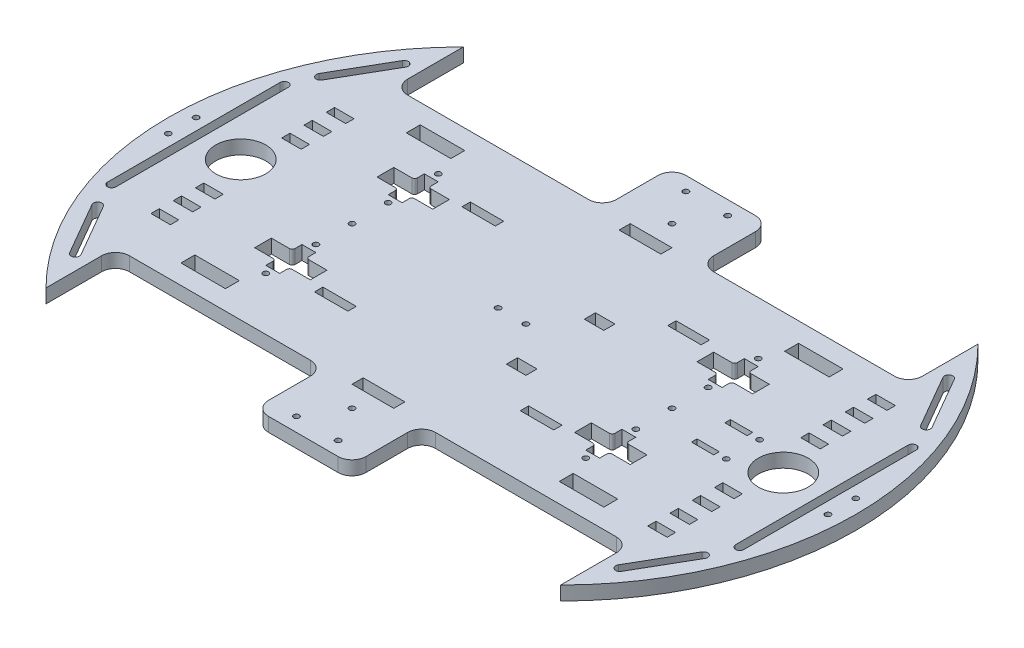
SolidWorks part; units mm, degrees
ref_plane "Front Plane" through (0, 0, 0) normal (0, 0, 1) x (1, 0, 0)
ref_plane "Top Plane" through (0, 0, 0) normal (0, 1, 0) x (1, 0, 0)
ref_plane "Right Plane" through (0, 0, 0) normal (1, 0, 0) x (0, 0, -1)
sketch "Sketch1" plane through (0, 0, 0) normal (0, 1, 0) x (1, 0, 0)
  line L2 (-12.5, 75) -> (12.5, 75)
  line L4 (-17.5, 70) -> (-17.5, 55)
  line L6 (-87.5, 50) -> (-22.5, 50)
  line L7 (87.5, 50) -> (22.5, 50)
  line L8 (17.5, 70) -> (17.5, 55)
  line L9 (-92.5, 55) -> (-92.5, 75)
  line L10 (92.5, 75) -> (92.5, 55)
  line L11 (92.5, -75) -> (92.5, -55)
  line L12 (-92.5, -55) -> (-92.5, -75)
  line L13 (17.5, -70) -> (17.5, -55)
  line L14 (87.5, -50) -> (22.5, -50)
  line L15 (-87.5, -50) -> (-22.5, -50)
  line L16 (-17.5, -70) -> (-17.5, -55)
  line L17 (-12.5, -75) -> (12.5, -75)
  arc A0 (-17.5, 55) -> (-22.5, 50) centre (-22.5, 55) cw
  arc A1 (17.5, 55) -> (22.5, 50) centre (22.5, 55) ccw
  arc A2 (-92.5, 55) -> (-87.5, 50) centre (-87.5, 55) ccw
  arc A3 (92.5, 55) -> (87.5, 50) centre (87.5, 55) cw
  arc A4 (92.5, -55) -> (87.5, -50) centre (87.5, -55) ccw
  arc A5 (-92.5, -55) -> (-87.5, -50) centre (-87.5, -55) cw
  arc A6 (17.5, -55) -> (22.5, -50) centre (22.5, -55) cw
  arc A7 (-17.5, -55) -> (-22.5, -50) centre (-22.5, -55) ccw
  arc A8 (92.5, -75) -> (92.5, 75) centre (17.5, 0) ccw
  arc A9 (-92.5, -75) -> (-92.5, 75) centre (-17.5, 0) cw
  arc A10 (12.5, -75) -> (17.5, -70) centre (12.5, -70) ccw
  arc A11 (-12.5, -75) -> (-17.5, -70) centre (-12.5, -70) cw
  arc A12 (12.5, 75) -> (17.5, 70) centre (12.5, 70) cw
  arc A13 (-12.5, 75) -> (-17.5, 70) centre (-12.5, 70) ccw
  point P20 (-92.5, 50)
  point P24 (92.5, 50)
  point P41 (92.5, -50)
  point P42 (-92.5, -50)
  point P47 (17.5, -75)
  point P50 (-17.5, -75)
  point P53 (17.5, 75)
  point P56 (-17.5, 75)
  dimension "D5" = 5
  dimension "D6" = 5
  dimension "D7" = 5
  dimension "D8" = 5
  dimension "D2" = 75
  dimension "D4" = 25
extrude "Boss-Extrude1" add sketch "Sketch1" along normal blind 5 contours L6 A0 L4 A13 L2 A12 L8 A1 L7 A3 L10 A8 L11 A4 L14 A6 L13 A10 L17 A11 L16 A7 L15 A5 L12 A9 L9 A2
sketch "Sketch2" plane through (0, 5, 0) normal (0, 1, 0) x (1, 0, 0)
  line L0 (-12.5, 75) -> (12.5, 75) construction
  line L1 (0, 31) -> (0, -27.6021)
  line L2 (-7.5, 50) -> (7.5, 50)
  line L3 (-7.5, 50) -> (-7.5, 46)
  line L4 (-7.5, 46) -> (7.5, 46)
  line L5 (7.5, 50) -> (7.5, 46)
  line L6 (-145.8755, 0) -> (156.3391, 0)
  line L7 (7.5, -50) -> (7.5, -46)
  line L8 (-7.5, -46) -> (7.5, -46)
  line L9 (-7.5, -50) -> (-7.5, -46)
  line L10 (-7.5, -50) -> (7.5, -50)
  line L11 (-92.5, 55) -> (-92.5, 75) construction
  line L12 (111.3751, -31) -> (111.3751, 31)
  line L14 (-111.3751, -31) -> (-111.3751, 31)
  line L16 (-114.3751, -31) -> (-114.3751, 31)
  line L17 (-111.3751, -32.5) -> (-114.3751, 32.5) construction
  line L18 (-111.3751, 32.5) -> (-114.3751, -32.5) construction
  line L19 (114.3751, -31) -> (114.3751, 31)
  line L20 (-87.5, 50) -> (-22.5, 50) construction
  line L21 (-96.7856, 25) -> (-89.7856, 25)
  line L22 (-96.7856, 25) -> (-96.7856, 22)
  line L23 (-96.7856, 22) -> (-89.7856, 22)
  line L24 (-89.7856, 25) -> (-89.7856, 22)
  line L25 (-96.7856, 25) -> (-89.7856, 22) construction
  line L26 (-96.7856, 22) -> (-89.7856, 25) construction
  line L27 (-89.7856, 30) -> (-96.7856, 30)
  line L28 (-89.7856, 30) -> (-89.7856, 33)
  line L29 (-89.7856, 33) -> (-96.7856, 33)
  line L30 (-96.7856, 30) -> (-96.7856, 33)
  line L31 (-89.7856, 30) -> (-96.7856, 33) construction
  line L32 (-89.7856, 33) -> (-96.7856, 30) construction
  line L33 (-89.7856, 14) -> (-96.7856, 14)
  line L34 (-89.7856, 14) -> (-89.7856, 17)
  line L35 (-89.7856, 17) -> (-96.7856, 17)
  line L36 (-96.7856, 14) -> (-96.7856, 17)
  line L37 (-89.7856, 14) -> (-96.7856, 17) construction
  line L38 (-89.7856, 17) -> (-96.7856, 14) construction
  line L39 (-89.7856, -17) -> (-96.7856, -14) construction
  line L40 (-89.7856, -14) -> (-96.7856, -17) construction
  line L41 (-89.7856, -33) -> (-96.7856, -30) construction
  line L42 (-89.7856, -30) -> (-96.7856, -33) construction
  line L43 (-96.7856, -22) -> (-89.7856, -25) construction
  line L44 (-96.7856, -25) -> (-89.7856, -22) construction
  line L45 (-96.7856, -14) -> (-96.7856, -17)
  line L46 (-89.7856, -17) -> (-96.7856, -17)
  line L47 (-89.7856, -14) -> (-89.7856, -17)
  line L48 (-89.7856, -14) -> (-96.7856, -14)
  line L49 (-96.7856, -30) -> (-96.7856, -33)
  line L50 (-89.7856, -33) -> (-96.7856, -33)
  line L51 (-89.7856, -30) -> (-89.7856, -33)
  line L52 (-89.7856, -30) -> (-96.7856, -30)
  line L53 (-89.7856, -25) -> (-89.7856, -22)
  line L54 (-96.7856, -22) -> (-89.7856, -22)
  line L55 (-96.7856, -25) -> (-96.7856, -22)
  line L56 (-96.7856, -25) -> (-89.7856, -25)
  line L57 (89.7856, 17) -> (96.7856, 14) construction
  line L58 (89.7856, 14) -> (96.7856, 17) construction
  line L59 (89.7856, 33) -> (96.7856, 30) construction
  line L60 (89.7856, 30) -> (96.7856, 33) construction
  line L61 (96.7856, 22) -> (89.7856, 25) construction
  line L62 (96.7856, 25) -> (89.7856, 22) construction
  line L63 (96.7856, 14) -> (96.7856, 17)
  line L64 (89.7856, 17) -> (96.7856, 17)
  line L65 (89.7856, 14) -> (89.7856, 17)
  line L66 (89.7856, 14) -> (96.7856, 14)
  line L67 (96.7856, 30) -> (96.7856, 33)
  line L68 (89.7856, 33) -> (96.7856, 33)
  line L69 (89.7856, 30) -> (89.7856, 33)
  line L70 (89.7856, 30) -> (96.7856, 30)
  line L71 (89.7856, 25) -> (89.7856, 22)
  line L72 (96.7856, 22) -> (89.7856, 22)
  line L73 (96.7856, 25) -> (96.7856, 22)
  line L74 (96.7856, 25) -> (89.7856, 25)
  line L75 (96.7856, -25) -> (89.7856, -22) construction
  line L76 (96.7856, -22) -> (89.7856, -25) construction
  line L77 (89.7856, -30) -> (96.7856, -33) construction
  line L78 (89.7856, -33) -> (96.7856, -30) construction
  line L79 (89.7856, -14) -> (96.7856, -17) construction
  line L80 (89.7856, -17) -> (96.7856, -14) construction
  line L81 (96.7856, -25) -> (89.7856, -25)
  line L82 (96.7856, -25) -> (96.7856, -22)
  line L83 (96.7856, -22) -> (89.7856, -22)
  line L84 (89.7856, -25) -> (89.7856, -22)
  line L85 (89.7856, -30) -> (96.7856, -30)
  line L86 (89.7856, -30) -> (89.7856, -33)
  line L87 (89.7856, -33) -> (96.7856, -33)
  line L88 (96.7856, -30) -> (96.7856, -33)
  line L89 (89.7856, -14) -> (96.7856, -14)
  line L90 (89.7856, -14) -> (89.7856, -17)
  line L91 (89.7856, -17) -> (96.7856, -17)
  line L92 (96.7856, -14) -> (96.7856, -17)
  line L93 (96.7856, -38) -> (89.7856, -41) construction
  line L94 (96.7856, 41) -> (89.7856, 41)
  line L95 (96.7856, 41) -> (96.7856, 38)
  line L96 (96.7856, 38) -> (89.7856, 38)
  line L97 (89.7856, 41) -> (89.7856, 38)
  line L98 (96.7856, 41) -> (89.7856, 38) construction
  line L99 (96.7856, 38) -> (89.7856, 41) construction
  line L100 (96.7856, -41) -> (89.7856, -38) construction
  line L101 (89.7856, -41) -> (89.7856, -38)
  line L102 (96.7856, -38) -> (89.7856, -38)
  line L103 (96.7856, -41) -> (96.7856, -38)
  line L104 (96.7856, -41) -> (89.7856, -41)
  line L105 (-54, 25) -> (-47.5, 25)
  line L106 (-60, 28.5) -> (-55, 28.5)
  line L107 (-60, 28.5) -> (-60, 26)
  line L108 (-60, 15.5) -> (-55, 15.5)
  line L109 (-55, 28.5) -> (-55, 26)
  line L110 (-67.5, 25) -> (-61, 25)
  line L111 (-67.5, 25) -> (-67.5, 19)
  line L112 (-67.5, 19) -> (-61, 19)
  line L113 (-47.5, 25) -> (-47.5, 19)
  line L114 (-60, 18) -> (-60, 15.5)
  line L115 (-54, 19) -> (-47.5, 19)
  line L116 (-55, 18) -> (-55, 15.5)
  line L117 (-17.5, 70) -> (-17.5, 55) construction
  line L118 (-55, -18) -> (-55, -15.5)
  line L119 (-54, -19) -> (-47.5, -19)
  line L120 (-60, -18) -> (-60, -15.5)
  line L121 (-47.5, -25) -> (-47.5, -19)
  line L122 (-67.5, -19) -> (-61, -19)
  line L123 (-67.5, -25) -> (-67.5, -19)
  line L124 (-67.5, -25) -> (-61, -25)
  line L125 (-55, -28.5) -> (-55, -26)
  line L126 (-60, -15.5) -> (-55, -15.5)
  line L127 (-60, -28.5) -> (-60, -26)
  line L128 (-60, -28.5) -> (-55, -28.5)
  line L129 (-54, -25) -> (-47.5, -25)
  line L130 (54, -25) -> (47.5, -25)
  line L131 (60, -28.5) -> (55, -28.5)
  line L132 (60, -28.5) -> (60, -26)
  line L133 (60, -15.5) -> (55, -15.5)
  line L134 (55, -28.5) -> (55, -26)
  line L135 (67.5, -25) -> (61, -25)
  line L136 (67.5, -25) -> (67.5, -19)
  line L137 (67.5, -19) -> (61, -19)
  line L138 (47.5, -25) -> (47.5, -19)
  line L139 (60, -18) -> (60, -15.5)
  line L140 (54, -19) -> (47.5, -19)
  line L141 (55, -18) -> (55, -15.5)
  line L142 (55, 18) -> (55, 15.5)
  line L143 (54, 19) -> (47.5, 19)
  line L144 (60, 18) -> (60, 15.5)
  line L145 (47.5, 25) -> (47.5, 19)
  line L146 (67.5, 19) -> (61, 19)
  line L147 (67.5, 25) -> (67.5, 19)
  line L148 (67.5, 25) -> (61, 25)
  line L149 (55, 28.5) -> (55, 26)
  line L150 (60, 15.5) -> (55, 15.5)
  line L151 (60, 28.5) -> (60, 26)
  line L152 (60, 28.5) -> (55, 28.5)
  line L153 (54, 25) -> (47.5, 25)
  line L154 (-42.9867, -28) -> (-42.9867, -25)
  line L155 (-42.9867, 28) -> (-30.9867, 28)
  line L156 (-42.9867, 28) -> (-42.9867, 25)
  line L157 (-42.9867, 25) -> (-30.9867, 25)
  line L158 (-30.9867, 28) -> (-30.9867, 25)
  line L159 (-42.9867, -25) -> (-30.9867, -25)
  line L160 (-30.9867, -28) -> (-30.9867, -25)
  line L161 (-42.9867, -28) -> (-30.9867, -28)
  line L162 (42.9867, 28) -> (42.9867, 25)
  line L163 (30.9867, 28) -> (30.9867, 25)
  line L164 (42.9867, 28) -> (30.9867, 28)
  line L165 (42.9867, 25) -> (30.9867, 25)
  line L166 (42.9867, -28) -> (30.9867, -28)
  line L167 (30.9867, -28) -> (30.9867, -25)
  line L168 (42.9867, -25) -> (30.9867, -25)
  line L169 (42.9867, -28) -> (42.9867, -25)
  line L170 (87.5, 50) -> (22.5, 50) construction
  line L171 (14, 16) -> (21, 16)
  line L172 (14, 16) -> (14, 12)
  line L173 (14, 12) -> (21, 12)
  line L174 (21, 16) -> (21, 12)
  line L175 (17.5, 70) -> (17.5, 55) construction
  line L176 (21, -16) -> (21, -12)
  line L177 (14, -12) -> (21, -12)
  line L178 (14, -16) -> (14, -12)
  line L179 (14, -16) -> (21, -16)
  line L180 (-110.1643, 40.799) -> (-99.1643, 59.8516)
  line L182 (-110.1643, -40.799) -> (-99.1643, -59.8516)
  line L184 (-107.5662, -39.299) -> (-96.5662, -58.3516)
  line L185 (-107.5662, 39.299) -> (-96.5662, 58.3516)
  line L186 (110.1643, 40.799) -> (99.1643, 59.8516)
  line L187 (107.5662, 39.299) -> (96.5662, 58.3516)
  line L188 (110.1643, -40.799) -> (99.1643, -59.8516)
  line L189 (107.5662, -39.299) -> (96.5662, -58.3516)
  circle A0 centre (0, 57.5) radius 1
  circle A1 centre (-7.5, 70) radius 1
  circle A2 centre (7.5, 70) radius 1
  circle A3 centre (7.5, -70) radius 1
  circle A4 centre (-7.5, -70) radius 1
  circle A5 centre (0, -57.5) radius 1
  circle A6 centre (-97.5, 0) radius 9
  arc A7 (-114.3751, 31) -> (-111.3751, 31) centre (-112.8751, 31) cw
  arc A8 (-114.3751, -31) -> (-111.3751, -31) centre (-112.8751, -31) ccw
  circle A9 centre (-118.566, 5) radius 1
  arc A10 (-92.5, 75) -> (-92.5, -75) centre (-17.5, 0) ccw construction
  circle A11 centre (-118.566, -5) radius 1
  circle A12 centre (118.566, -5) radius 1
  circle A13 centre (118.566, 5) radius 1
  arc A14 (114.3751, 31) -> (111.3751, 31) centre (112.8751, 31) ccw
  arc A15 (114.3751, -31) -> (111.3751, -31) centre (112.8751, -31) cw
  circle A16 centre (97.5, 0) radius 9
  arc A17 (-55, 26) -> (-54, 25) centre (-54, 26) ccw
  arc A18 (-54, 19) -> (-55, 18) centre (-54, 18) ccw
  arc A19 (-60, 18) -> (-61, 19) centre (-61, 18) ccw
  arc A20 (-61, 25) -> (-60, 26) centre (-61, 26) ccw
  arc A21 (-61, -25) -> (-60, -26) centre (-61, -26) cw
  arc A22 (-60, -18) -> (-61, -19) centre (-61, -18) cw
  arc A23 (-54, -19) -> (-55, -18) centre (-54, -18) cw
  arc A24 (-55, -26) -> (-54, -25) centre (-54, -26) cw
  arc A25 (55, -26) -> (54, -25) centre (54, -26) ccw
  arc A26 (54, -19) -> (55, -18) centre (54, -18) ccw
  arc A27 (60, -18) -> (61, -19) centre (61, -18) ccw
  arc A28 (61, -25) -> (60, -26) centre (61, -26) ccw
  arc A29 (61, 25) -> (60, 26) centre (61, 26) cw
  arc A30 (60, 18) -> (61, 19) centre (61, 18) cw
  arc A31 (54, 19) -> (55, 18) centre (54, 18) cw
  arc A32 (55, 26) -> (54, 25) centre (54, 26) cw
  circle A34 centre (5, 0) radius 1
  circle A35 centre (-5, 0) radius 1
  arc A36 (-110.1643, -40.799) -> (-107.5662, -39.299) centre (-108.8653, -40.049) cw
  arc A37 (-99.1643, -59.8516) -> (-96.5662, -58.3516) centre (-97.8653, -59.1016) ccw
  arc A38 (-99.1643, 59.8516) -> (-96.5662, 58.3516) centre (-97.8653, 59.1016) cw
  arc A39 (-110.1643, 40.799) -> (-107.5662, 39.299) centre (-108.8653, 40.049) ccw
  arc A40 (110.1643, 40.799) -> (107.5662, 39.299) centre (108.8653, 40.049) cw
  arc A41 (99.1643, 59.8516) -> (96.5662, 58.3516) centre (97.8653, 59.1016) ccw
  arc A42 (110.1643, -40.799) -> (107.5662, -39.299) centre (108.8653, -40.049) ccw
  arc A43 (99.1643, -59.8516) -> (96.5662, -58.3516) centre (97.8653, -59.1016) cw
  circle A44 centre (83.0203, 6) radius 1
  circle A45 centre (83.0203, -6) radius 1
  circle A46 centre (57.5, 0) radius 1
  circle A47 centre (57.5, 13) radius 1
  circle A48 centre (57.5, -13) radius 1
  circle A49 centre (57.5, 31) radius 1
  circle A50 centre (57.5, -31) radius 1
  circle A51 centre (-57.5, -31) radius 1
  circle A52 centre (-57.5, -13) radius 1
  circle A53 centre (-57.5, 0) radius 1
  circle A54 centre (-57.5, 13) radius 1
  circle A55 centre (-57.5, 31) radius 1
  point P27 (-112.8751, 0)
  point P38 (-123.566, 0)
  point P62 (-93.2856, 23.5)
  point P67 (-93.2856, 31.5)
  point P72 (-93.2856, 15.5)
  point P91 (-93.2856, -15.5)
  point P92 (-93.2856, -31.5)
  point P93 (-93.2856, -23.5)
  point P106 (93.2856, 15.5)
  point P107 (93.2856, 31.5)
  point P108 (93.2856, 23.5)
  point P121 (93.2856, -23.5)
  point P122 (93.2856, -31.5)
  point P123 (93.2856, -15.5)
  point P124 (93.2856, 39.5)
  point P133 (93.2856, -39.5)
  point P150 (-55, 19)
  point P177 (-55, -19)
  point P198 (55, -19)
  point P219 (55, 19)
  point P252 (-97.8653, -59.1016)
  point P253 (-104.6643, -50.3253)
  point P266 (-104.6643, 50.3253)
  dimension "D1" = 17.5
  dimension "D2" = 5
  dimension "D7" = 5
  dimension "D10" = 5
  dimension "D27" = 1
  dimension "D33" = 5
  dimension "D38" = 6
  dimension "D39" = 2.5
  dimension "D3" = 5
  dimension "D4" = 7.5
  dimension "D5" = 7.5
  dimension "D6" = 4
  dimension "D8" = 65
  dimension "D9" = 3
  dimension "D11" = 5
  dimension "D12" = 7
  dimension "D13" = 3
  dimension "D14" = 3
  dimension "D15" = 3
  dimension "D16" = 20
  dimension "D17" = 8
  dimension "D18" = 8
  dimension "D19" = 3
  dimension "D20" = 11
  dimension "D21" = 5
  dimension "D22" = 13
  dimension "D23" = 20
  dimension "D24" = 6
  dimension "D25" = 7.5
  dimension "D26" = 3.5
  dimension "D28" = 25
  dimension "D29" = 30
  dimension "D30" = 12
  dimension "D31" = 3
  dimension "D32" = 22
  dimension "D34" = 4
  dimension "D35" = 7
  dimension "D36" = 34
  dimension "D37" = 3.5
extrude "Cut-Extrude1" cut sketch "Sketch2" against normal blind 5 contours L180 A39 L185 A38 | L6 A6 | L6 A6 | L182 A37 L184 A36 | L125 A24 L129 L121 L119 A23 L118 L126 L120 A22 L122 L123 L124 A21 L127 L128 | L14 A7 L16 A8 | L28 L29 L30 L27 | L24 L23 L22 L21 | L33 L36 L35 L34 | L46 L45 L48 L47 | L54 L53 L56 L55 | L52 L49 L50 L51 region at (-97.5, 5, -3.8197) region at (-97.5, 5, 3.8197) region at (-57.5, 5, 22) region at (-103.3653, 5, -49.5753) region at (-103.3653, 5, 49.5753)
extrude "Cut-Extrude2" cut sketch "Sketch2<3>" against normal blind 5 contours A20 L110 L111 L112 A19 L114 L108 L116 A18 L115 L113 L105 A17 L109 L106 L107 | L158 L155 L156 L157 | L154 L161 L160 L159 | L9 L10 L7 L8 | A2 | A1 | L178 L179 L176 L177 | L174 L171 L172 L173 | A28 L135 L136 L137 A27 L139 L133 L141 A26 L140 L138 L130 A25 L134 L131 L132 | L149 A32 L153 L145 L143 A31 L142 L150 L144 A30 L146 L147 L148 A29 L151 L152 | A48 | A50 | L88 L85 L86 L87 | L84 L81 L82 L83 | L92 L89 L90 L91 | A16 L6 | A16 L6 | L19 A14 L12 L6 | A15 L19 L6 L12 | L186 A41 L187 A40 | A9 | A11 | A55 | A54 | A53 | A51 | A52 | A5 | A3 | A4 | L2 L5 L4 L3 | A0 | A34 | A35 | L164 L163 L165 L162 | L168 L167 L166 L169 | A49 | A47 | A46 | L103 L102 L101 L104 | A45 | A44 | L64 L63 L66 L65 | L74 L71 L72 L73 | L68 L67 L70 L69 | L96 L97 L94 L95 | A13 | A12 | L189 A43 L188 A42 region at (112.8751, 5, -16.0908) region at (112.8751, 5, 16.0908) region at (97.5, 5, -3.8197) region at (97.5, 5, 3.8197) region at (0, 5, 48) region at (93.2856, 5, 23.5) region at (93.2856, 5, 31.5) region at (93.2856, 5, 15.5) region at (-57.5, 5, -22) region at (57.5, 5, 22) region at (57.5, 5, -22) region at (-36.9867, 5, 26.5) region at (-36.9867, 5, -26.5) region at (17.5, 5, -14) region at (17.5, 5, 14) region at (103.3653, 5, -49.5753) region at (-7.5, 5, -70) region at (7.5, 5, -70) region at (57.5, 5, 13) region at (57.5, 5, 31)
sketch "Sketch2<3>" plane through (0, 5, 0) normal (0, 1, 0) x (1, 0, 0) same geometry as "Sketch2"
sketch "Sketch5" plane through (0, 5, 0) normal (0, 1, 0) x (1, 0, 0)
  line L2 (87.5, 50) -> (22.5, 50) construction
  line L3 (60, 43) -> (76, 43)
  line L4 (60, 43) -> (60, 38)
  line L5 (60, 38) -> (76, 38)
  line L6 (76, 43) -> (76, 38)
  line L7 (60, -43) -> (60, -38)
  line L8 (60, -38) -> (76, -38)
  line L9 (76, -43) -> (76, -38)
  line L10 (60, -43) -> (76, -43)
  line L11 (-60, -43) -> (-60, -38)
  line L12 (-60, -43) -> (-76, -43)
  line L13 (-60, -38) -> (-76, -38)
  line L14 (-76, -43) -> (-76, -38)
  line L15 (-60, 38) -> (-76, 38)
  line L16 (-60, 43) -> (-60, 38)
  line L17 (-60, 43) -> (-76, 43)
  line L18 (-76, 43) -> (-76, 38)
  dimension "D1" = 16
  dimension "D2" = 5
  dimension "D3" = 7
extrude "Cut-Extrude3" cut sketch "Sketch5" against normal blind 10
sketch "Sketch6" plane through (0, 5, 0) normal (0, 1, 0) x (1, 0, 0)
  line L0 (0, 0) -> (100.8284, 0)
  line L1 (0, 0) -> (0, 96.869)
  line L2 (79.501, -5) -> (79.501, -7)
  line L3 (79.501, 5) -> (71.501, 5)
  line L4 (79.501, 5) -> (79.501, 7)
  line L5 (79.501, 7) -> (71.501, 7)
  line L6 (71.501, 5) -> (71.501, 7)
  line L7 (79.501, 5) -> (71.501, 7) construction
  line L8 (79.501, 7) -> (71.501, 5) construction
  line L9 (79.501, -5) -> (71.501, -5)
  line L10 (71.501, -5) -> (71.501, -7)
  line L11 (79.501, -7) -> (71.501, -7)
  point P4 (75.501, 6)
  dimension "D1" = 2
  dimension "D2" = 8
extrude "Cut-Extrude4" cut sketch "Sketch6" against normal blind 10 contours L3 L6 L5 L4 | L9 L10 L11 L2
